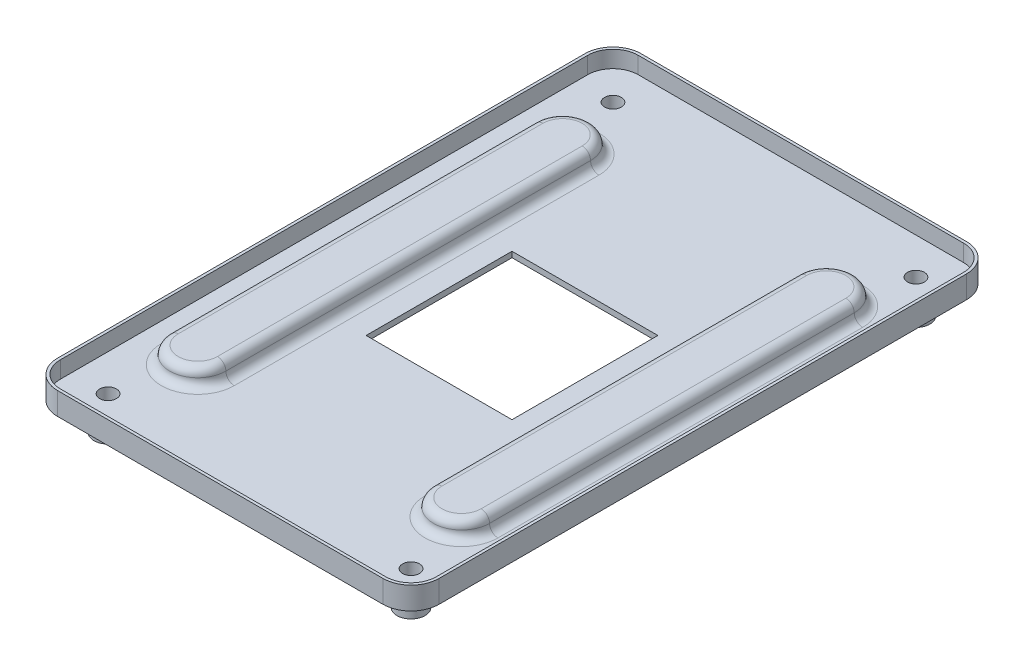
SolidWorks part; units mm, degrees
ref_plane "Front Plane" through (0, 0, 0) normal (0, 0, 1) x (1, 0, 0)
ref_plane "Top Plane" through (0, 0, 0) normal (0, 1, 0) x (1, 0, 0)
ref_plane "Right Plane" through (0, 0, 0) normal (1, 0, 0) x (0, 0, -1)
sketch "Sketch1" plane through (0, 0, 0) normal (0, 1, 0) x (1, 0, 0)
  line L1 (-34, -52) -> (34, -52)
  line L2 (-34, -52) -> (-34, 52)
  line L3 (-34, 52) -> (34, 52)
  line L4 (34, -52) -> (34, 52)
  line L5 (-34, -52) -> (34, 52) construction
  line L6 (-34, 52) -> (34, -52) construction
  line L7 (-13, -13) -> (13, -13)
  line L8 (-13, -13) -> (-13, 13)
  line L9 (-13, 13) -> (13, 13)
  line L10 (13, -13) -> (13, 13)
  line L11 (-13, -13) -> (13, 13) construction
  line L12 (-13, 13) -> (13, -13) construction
  point P0 (0, 0)
  point P6 (0, 0)
  dimension "D1" = 68
  dimension "D2" = 104
  dimension "D3" = 26
  dimension "D4" = 26
extrude "Boss-Extrude1" add sketch "Sketch1" along normal blind 4
fillet "Fillet1" radius 5 4 edges at (-34, 2, -52) (34, 2, -52) (34, 2, 52) (-34, 2, 52)
sketch "Sketch3" plane through (0, 4, 0) normal (0, 1, 0) x (1, 0, 0)
  line L4 (-23.5, -32.5) -> (-23.5, 32.5) construction
  line L5 (-28.5, -32.5) -> (-28.5, 32.5)
  line L6 (-18.5, -32.5) -> (-18.5, 32.5)
  line L7 (23.5, -32.5) -> (23.5, 32.5) construction
  line L8 (29, 51.5) -> (-29, 51.5)
  line L9 (-33.5, 47) -> (-33.5, -47)
  line L10 (-29, -51.5) -> (29, -51.5)
  line L11 (33.5, -47) -> (33.5, 47)
  line L12 (29, 51.5) -> (-29, 51.5)
  line L13 (-33.5, 47) -> (-33.5, -47)
  line L14 (-29, -51.5) -> (29, -51.5)
  line L15 (33.5, -47) -> (33.5, 47)
  line L16 (18.5, -32.5) -> (18.5, 32.5)
  line L17 (28.5, -32.5) -> (28.5, 32.5)
  arc A4 (-28.5, -32.5) -> (-18.5, -32.5) centre (-23.5, -32.5) ccw
  arc A5 (-18.5, 32.5) -> (-28.5, 32.5) centre (-23.5, 32.5) ccw
  arc A6 (18.5, -32.5) -> (28.5, -32.5) centre (23.5, -32.5) ccw
  arc A7 (28.5, 32.5) -> (18.5, 32.5) centre (23.5, 32.5) ccw
  arc A8 (-29, 51.5) -> (-33.5, 47) centre (-29, 47) ccw
  arc A9 (-33.5, -47) -> (-29, -51.5) centre (-29, -47) ccw
  arc A10 (29, -51.5) -> (33.5, -47) centre (29, -47) ccw
  arc A11 (33.5, 47) -> (29, 51.5) centre (29, 47) ccw
  arc A12 (-29, 51.5) -> (-33.5, 47) centre (-29, 47) ccw
  arc A13 (-33.5, -47) -> (-29, -51.5) centre (-29, -47) ccw
  arc A14 (29, -51.5) -> (33.5, -47) centre (29, -47) ccw
  arc A15 (33.5, 47) -> (29, 51.5) centre (29, 47) ccw
  point P2 (-23.5, 0)
  point P9 (23.5, 0)
  dimension "D2" = 10
  dimension "D3" = 10
  dimension "D4" = 5
  dimension "D5" = 5
  dimension "D6" = 65
  dimension "D7" = 65
  dimension "D8" = 32.5
  dimension "D9" = 32.5
  dimension "D1" = 0.5
extrude "Cut-Extrude1" cut sketch "Sketch3" against normal blind 3
fillet "Fillet2" radius 1.5 16 edges at (23.5, 4, -37.5) (28.5, 4, 0) (23.5, 4, 37.5) (23.5, 1, -37.5) (28.5, 1, 0) (23.5, 1, 37.5) (-23.5, 4, -37.5) (-18.5, 4, 0) (-23.5, 4, 37.5) (-23.5, 1, -37.5) (-18.5, 1, 0) (-23.5, 1, 37.5) (18.5, 4, 0) (18.5, 1, 0) (-28.5, 4, 0) (-28.5, 1, 0)
sketch "Sketch4" plane through (0, 0, 0) normal (0, -1, 0) x (1, 0, 0)
  circle A0 centre (-27, 45) radius 2.5
  circle A1 centre (27, 45) radius 2.5
  circle A2 centre (27, -45) radius 2.5
  circle A3 centre (-27, -45) radius 2.5
  dimension "D1" = 5
  dimension "D2" = 5
  dimension "D3" = 5
  dimension "D4" = 5
  dimension "D5" = 54
  dimension "D6" = 54
  dimension "D7" = 90
  dimension "D8" = 90
  dimension "D9" = 45
  dimension "D10" = 45
  dimension "D11" = 27
  dimension "D12" = 27
extrude "Boss-Extrude2" add sketch "Sketch4" along normal blind 5
sketch "Sketch5" plane through (0, -5, 0) normal (0, -1, 0) x (1, 0, 0)
  circle A0 centre (-27, 45) radius 1.5
  circle A1 centre (27, 45) radius 1.5
  circle A2 centre (27, -45) radius 1.5
  circle A3 centre (-27, -45) radius 1.5
  dimension "D1" = 3
  dimension "D2" = 3
  dimension "D3" = 3
  dimension "D4" = 3
extrude "Cut-Extrude2" cut sketch "Sketch5" against normal through all
